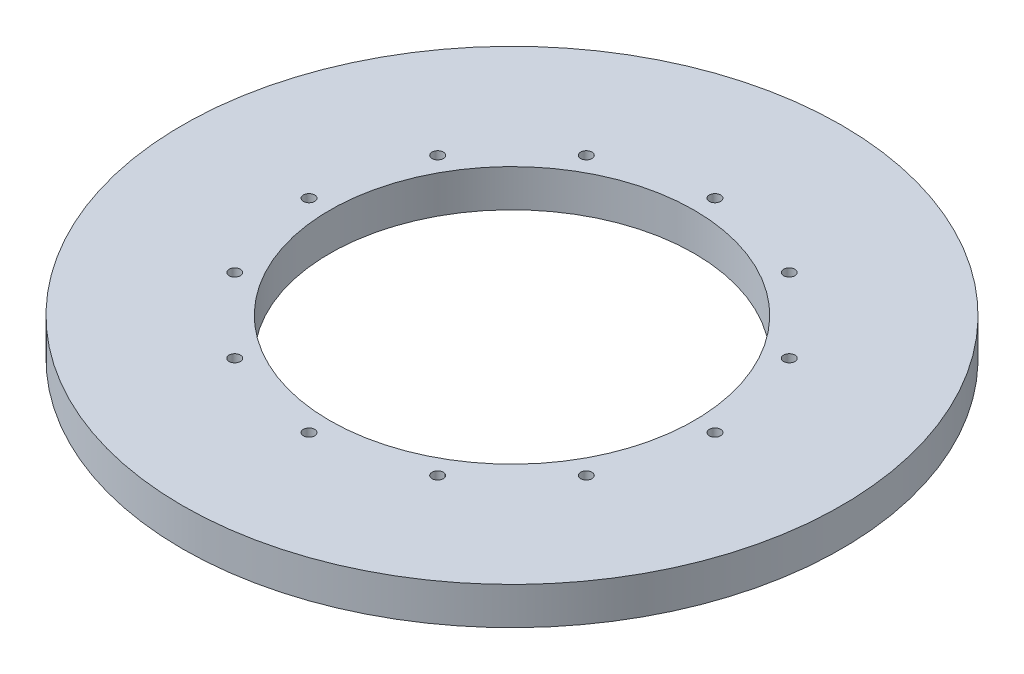
SolidWorks part; units mm, degrees
material "6061-T6 (SS)"
ref_plane "Front Plane" through (0, 0, 0) normal (0, 0, 1) x (1, 0, 0)
ref_plane "Top Plane" through (0, 0, 0) normal (0, 1, 0) x (1, 0, 0)
ref_plane "Right Plane" through (0, 0, 0) normal (1, 0, 0) x (0, 0, -1)
sketch "Sketch1" plane through (0, 0, 0) normal (0, 1, 0) x (1, 0, 0)
  line L5 (0, 0) -> (127.635, 0)
  line L6 (0, 0) -> (0, 127.635)
  line L7 (0, 127.635) -> (127.635, 127.635)
  line L8 (127.635, 0) -> (127.635, 127.635)
  dimension "D1" = 127.635
  dimension "D2" = 127.635
extrude "Boss-Extrude1" add sketch "Sketch1" along normal blind 9.525 contours L5 L8 L7 L6
sketch "Sketch12" plane through (0, 0, 0) normal (0, -1, 0) x (1, 0, 0)
  line L0 (63.8175, 0) -> (63.8175, -127.635) construction
  line L1 (0, 0) -> (127.635, 0) construction
  line L2 (0, -127.635) -> (127.635, -127.635) construction
  line L3 (0, -63.8175) -> (127.635, -63.8175) construction
  line L4 (0, 0) -> (0, -127.635) construction
  line L5 (127.635, 0) -> (127.635, -127.635) construction
  circle A0 centre (63.8175, -63.8175) radius 83.82
  dimension "D1" = 167.64
extrude "Boss-Extrude2" add sketch "Sketch12" against normal up to surface (9.525 mm away) contours A0 up to face at (63.8175, 9.525, -63.8175)
sketch "Sketch13" plane through (0, 0, 0) normal (0, -1, 0) x (-1, 0, 0)
  circle A0 centre (-63.8175, 63.8175) radius 83.82
  circle A1 centre (-63.8175, 63.8175) radius 104.9285
  dimension "D1" = 167.64
extrude "Cut-Extrude4" cut sketch "Sketch13" against normal up to surface (9.525 mm away) contours A1 | A0 up to face at (63.8175, 9.525, -63.8175)
sketch "Sketch5" plane through (0, 9.525, 0) normal (0, 1, 0) x (1, 0, 0)
  circle A0 centre (63.8175, 63.8175) radius 46.355
  circle A1 centre (63.8175, 63.8175) radius 83.82 construction
  point P8 (0, 0)
  dimension "D1" = 92.71
extrude "Cut-Extrude1" cut sketch "Sketch5" against normal blind 9.525
sketch "Sketch11" plane through (0, 9.525, 0) normal (0, 1, 0) x (1, 0, 0)
  line L0 (63.8175, 63.8175) -> (63.8175, 115.443) construction
  circle A0 centre (63.8175, 115.443) radius 1.4351
  dimension "D2" = 2.8702
  dimension "D1" = 51.6255
extrude "Cut-Extrude3" cut sketch "Sketch11" against normal through all contours A0
pattern_circular "CirPattern1" count 12 over 360 about axis through (63.8175, 9.525, -63.8175) along (0, 1, 0) of "Cut-Extrude3"
